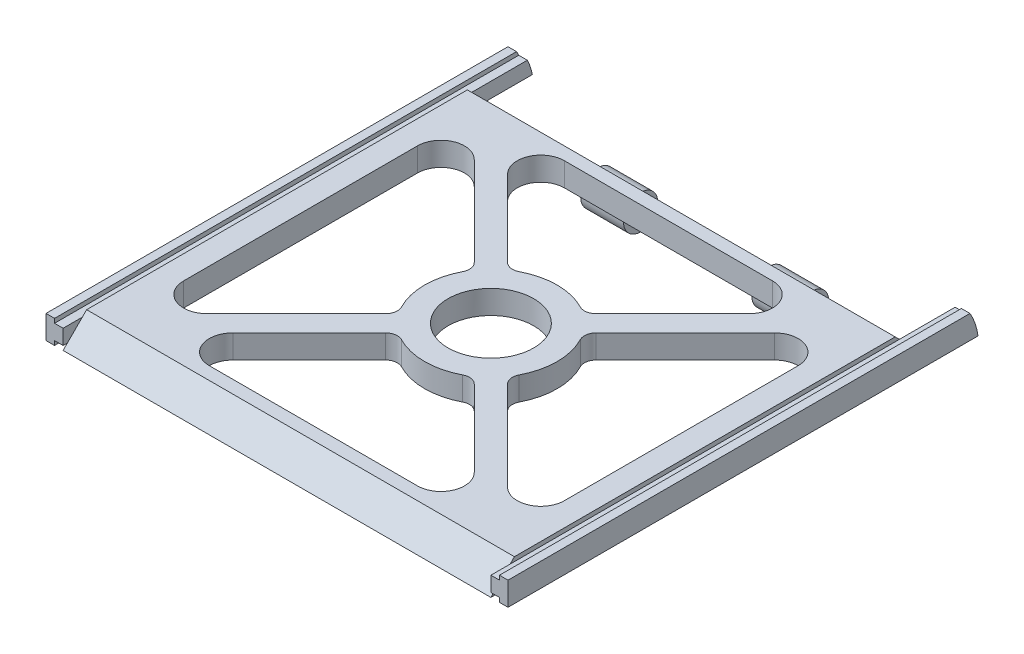
SolidWorks part; units mm, degrees
material "Alumina"
ref_plane "Front Plane" through (0, 0, 0) normal (0, 0, 1) x (1, 0, 0)
ref_plane "Top Plane" through (0, 0, 0) normal (0, 1, 0) x (1, 0, 0)
ref_plane "Right Plane" through (0, 0, 0) normal (1, 0, 0) x (0, 0, -1)
sketch "Sketch1" plane through (0, 0, 0) normal (0, 1, 0) x (1, 0, 0)
  line L0 (0, 110) -> (4, 110)
  line L1 (0, 0) -> (108, 0)
  line L2 (0, 0) -> (0, 110)
  line L4 (108, 0) -> (108, 110)
  line L5 (4, 110) -> (4, 100)
  line L6 (4, 100) -> (104, 100)
  line L7 (104, 100) -> (104, 110)
  line L8 (104, 110) -> (108, 110)
  dimension "D1" = 110
  dimension "D2" = 108
  dimension "D3" = 4
  dimension "D4" = 4
  dimension "D5" = 10
  dimension "D6" = 10
extrude "Boss-Extrude1" add sketch "Sketch1" along normal blind 5.5
sketch "Sketch4" plane through (0, 0, -110) normal (0, 0, -1) x (-1, 0, 0)
  line L1 (-4, 0) -> (-2, 0)
  line L2 (-4, 0) -> (-4, 1)
  line L3 (-4, 1) -> (-2, 1)
  line L4 (-2, 0) -> (-2, 1)
  line L5 (-4, 5.5) -> (-2, 5.5)
  line L6 (-4, 5.5) -> (-4, 4.5)
  line L7 (-4, 4.5) -> (-2, 4.5)
  line L8 (-2, 5.5) -> (-2, 4.5)
  line L9 (-104, 5.5) -> (-106, 5.5)
  line L10 (-104, 5.5) -> (-104, 4.5)
  line L11 (-104, 4.5) -> (-106, 4.5)
  line L12 (-106, 5.5) -> (-106, 4.5)
  line L13 (-104, 0) -> (-106, 0)
  line L14 (-104, 0) -> (-104, 1)
  line L15 (-104, 1) -> (-106, 1)
  line L16 (-106, 0) -> (-106, 1)
  dimension "D1" = 2
  dimension "D2" = 2
  dimension "D3" = 2
  dimension "D4" = 2
  dimension "D5" = 1
  dimension "D6" = 1
  dimension "D7" = 1
  dimension "D8" = 1
extrude "Cut-Extrude2" cut sketch "Sketch4" against normal blind 110
sketch "Sketch5" plane through (0, 5.5, 0) normal (0, 1, 0) x (1, 0, 0)
  line L0 (0, 0) -> (54, 0) construction
  line L1 (4, 0) -> (104, 0) construction
  line L2 (54, 0) -> (54, 100) construction
  line L3 (104, 100) -> (4, 100) construction
  line L4 (54, 50) -> (22.1802, 18.1802) construction
  line L5 (54, 50) -> (22.1802, 81.8198) construction
  line L6 (41.2692, 41.1583) -> (9.5, 9.3891)
  line L7 (9.5, 9.3891) -> (9.5, 90.6109)
  line L8 (9.5, 90.6109) -> (41.2692, 58.8417)
  line L9 (4, 0) -> (4, 100) construction
  line L14 (98.5, 90.6109) -> (98.5, 9.3891)
  line L15 (66.7308, 58.8417) -> (98.5, 90.6109)
  line L16 (98.5, 9.3891) -> (66.7308, 41.1583)
  line L20 (13.3891, 94.5) -> (94.6109, 94.5) [skipped]
  line L21 (45.1583, 62.7308) -> (13.3891, 94.5) [skipped]
  line L22 (94.6109, 94.5) -> (62.8417, 62.7308) [skipped]
  line L23 (62.8417, 37.2692) -> (94.6109, 5.5) [skipped]
  line L24 (13.3891, 5.5) -> (45.1583, 37.2692) [skipped]
  line L25 (94.6109, 5.5) -> (13.3891, 5.5) [skipped]
  line L26 (45.1583, 62.7308) -> (16.3891, 91.5)
  line L27 (16.3891, 91.5) -> (91.6109, 91.5)
  line L28 (91.6109, 91.5) -> (62.8417, 62.7308)
  line L29 (54, 50) -> (64, 50) construction
  line L30 (16.3891, 8.5) -> (91.6109, 8.5)
  line L31 (91.6109, 8.5) -> (62.8417, 37.2692)
  line L32 (45.1583, 37.2692) -> (16.3891, 8.5)
  circle A0 centre (54, 50) radius 10
  arc A1 (41.2692, 58.8417) -> (41.2692, 41.1583) centre (54, 50) ccw
  arc A3 (66.7308, 41.1583) -> (66.7308, 58.8417) centre (54, 50) ccw
  arc A5 (62.8417, 62.7308) -> (45.1583, 62.7308) centre (54, 50) ccw [skipped]
  arc A6 (45.1583, 37.2692) -> (62.8417, 37.2692) centre (54, 50) ccw [skipped]
  arc A7 (45.1583, 62.7308) -> (62.8417, 62.7308) centre (54, 50) cw
  arc A8 (45.1583, 37.2692) -> (62.8417, 37.2692) centre (54, 50) ccw
  point P34 (54, 50)
  dimension "D1" = 20
  dimension "D7" = 15.5
  dimension "D9" = 15.5
  dimension "D2" = 45
  dimension "D3" = 45
  dimension "D4" = 2.75
  dimension "D5" = 2.75
  dimension "D6" = 5.5
  dimension "D10" = 8.5
  dimension "D11" = 2.75
  dimension "D12" = 5.5
  dimension "D13" = 10
  dimension "D14" = 45
  dimension "D15" = 45
  dimension "D8" = 4
extrude "Cut-Extrude3" cut sketch "Sketch5" against normal blind 110
sketch "Sketch6" plane through (108, 0, 0) normal (1, 0, 0) x (0, 0, -1)
  line L0 (0, 0) -> (5.5, 5.5)
  line L1 (0, 5.5) -> (110, 5.5) construction
  line L2 (5.5, 5.5) -> (0, 5.5)
  line L3 (0, 5.5) -> (0, 0)
  line L4 (100, 5.5) -> (100, 0)
  line L9 (0, 0) -> (110, 0) construction
  line L10 (100, 0) -> (94.5, 5.5)
  line L11 (94.5, 5.5) -> (100, 5.5)
  line L12 (110, 5.5) -> (110, 0) construction
  dimension "D1" = 45
  dimension "D2" = 10
  dimension "D3" = 45
extrude "Cut-Extrude4" cut sketch "Sketch6" against normal blind 100 from offset 4 offset against normal yes
fillet "Fillet3" radius 5.5 8 edges at (91.6109, 2.75, -8.5) (98.5, 2.75, -9.3891) (98.5, 2.75, -90.6109) (91.6109, 2.75, -91.5) (16.3891, 2.75, -91.5) (9.5, 2.75, -90.6109) (9.5, 2.75, -9.3891) (16.3891, 2.75, -8.5)
fillet "Fillet4" radius 2.75 8 edges at (66.7308, 2.75, -41.1583) (66.7308, 2.75, -58.8417) (62.8417, 2.75, -62.7308) (45.1583, 2.75, -62.7308) (41.2692, 2.75, -41.1583) (41.2692, 2.75, -58.8417) (62.8417, 2.75, -37.2692) (45.1583, 2.75, -37.2692)
sketch "Sketch7" plane through (108, 0, 0) normal (1, 0, 0) x (0, 0, -1)
  line L0 (110, 0) -> (100, 0) construction
  line L2 (100, 0) -> (100, -4.5) construction
  line L3 (100, 0) -> (97, 0)
  line L4 (0, 0) -> (110, 0) construction
  line L5 (97, 0) -> (97, -1.8542)
  line L6 (100, 0) -> (100, -0.5)
  circle A0 centre (100, -4.5) radius 2
  arc A2 (100, -0.5) -> (97, -1.8542) centre (100, -4.5) cw
  dimension "D2" = 3
  dimension "D3" = 4
  dimension "D1" = 4.5
  dimension "D4" = 0.5
extrude "Boss-Extrude2" add sketch "Sketch7" against normal blind 10 from offset 29 offset against normal yes
extrude "Boss-Extrude3" add sketch "Sketch7<3>" against normal blind 10 from offset 69 offset against normal yes
sketch "Sketch7<3>" plane through (108, 0, 0) normal (1, 0, 0) x (0, 0, -1) same geometry as "Sketch7"
sketch "Sketch9" plane through (108, 0, 0) normal (1, 0, 0) x (0, 0, -1)
  line L0 (110, -2) -> (115, -2)
  line L1 (115, -2) -> (115, 18)
  line L3 (115, 18) -> (95, 18)
  line L5 (95, 18) -> (95, 13)
  arc A1 (95, 13) -> (110, -2) centre (95, -2) cw
  dimension "D3" = 15
  dimension "D1" = 5
  dimension "D2" = 5
extrude "Cut-Extrude5" cut sketch "Sketch9" against normal through all
